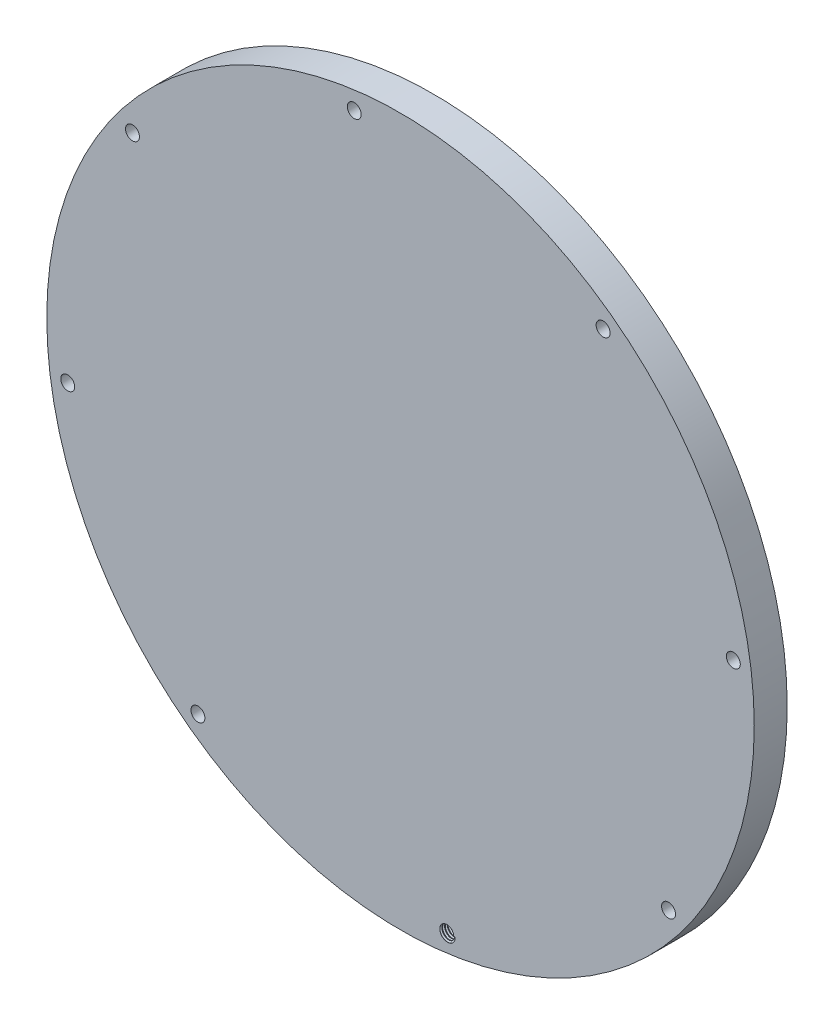
SolidWorks part; units mm, degrees
material "PVC rigide"
ref_plane "Plan de face" through (0, 0, 0) normal (0, 0, 1) x (1, 0, 0)
ref_plane "Plan de dessus" through (0, 0, 0) normal (0, 1, 0) x (1, 0, 0)
ref_plane "Plan de droite" through (0, 0, 0) normal (1, 0, 0) x (0, 0, -1)
sketch "Esquisse1" plane through (0, 0, 0) normal (0, 0, 1) x (1, 0, 0)
  circle A0 centre (0, 0) radius 139.5
  dimension "D1" = 279
extrude "Disque" add sketch "Esquisse1" along normal blind 13
sketch "Esquisse2" plane through (0, 0, 0) normal (0, 0, -1) x (-1, 0, 0)
  circle A0 centre (-79.8952, 105.7025) radius 2.75
  circle A1 centre (18.2485, 131.2373) radius 2.75
  circle A2 centre (105.7025, 79.8952) radius 2.75
  circle A3 centre (131.2373, -18.2485) radius 2.75
  circle A4 centre (79.8952, -105.7025) radius 2.75
  circle A5 centre (-18.2485, -131.2373) radius 2.75
  circle A6 centre (-105.7025, -79.8952) radius 2.75
  circle A7 centre (-131.2373, 18.2485) radius 2.75
  point P20 (0, 0)
  dimension "D1" = 5.5
  dimension "D2" = 132.5
  dimension "D4" = 0
  dimension "D3" = 8
extrude "Pas_De_Vis" cut sketch "Esquisse2" against normal blind 13
sketch "Esquisse4" plane through (0, 0, 0) normal (0, 0, -1) x (-1, 0, 0)
  circle A0 centre (0, 0) radius 120
  dimension "D1" = 240
extrude "Bain" cut sketch "Esquisse4" against normal blind 3
thread "Filetage1" pitch 1.0583 method cut profile "Profil de filetage1" start angle 0, offset 0, length 0, pitch 1.0583, diameter 5.5
ref_plane "Plan1" through (20.9985, -131.2373, 0) normal (0, -1, 0) x (1, 0, 0)
sketch "Profil de filetage1" plane through (20.9985, -131.2373, 0) normal (0, -1, 0) x (1, 0, 0)
  line L0 (0, 0) -> (0, 1.0583) construction
  line L1 (0, 0) -> (0.5728, 0.3307)
  line L2 (0.5728, 0.3307) -> (0.5728, 0.463)
  line L3 (0.5728, 0.463) -> (0, 0.7937)
  line L4 (0.5728, 0.3969) -> (0, 0.3969) construction
  line L11 (0, 0) -> (0, 0.7937)
  point P2 (0, 0)
  dimension "Pitch" = 1.0583
  dimension "Profile_Angle" = 60
  dimension "Profile_Land" = 0.1323
  dimension "Profile_Height" = 0.5728
sketch "Milieu" plane through (0, 0, 3) normal (0, 0, -1) x (-1, 0, 0)
  line L0 (0, -28.5) -> (0, 28.5) construction
  line L3 (28.5, -28.5) -> (28.5, 28.5)
  line L4 (-28.5, -28.5) -> (-28.5, 28.5)
  arc A0 (28.5, 28.5) -> (-28.5, 28.5) centre (0, 28.5) ccw
  arc A1 (28.5, -28.5) -> (-28.5, -28.5) centre (0, -28.5) cw
  point P7 (0, 0)
  point P8 (0, 28.5)
  dimension "D4" = 28.5
  dimension "D5" = 28.5
  dimension "D1" = 57
  dimension "D2" = 0
  dimension "D3" = 0
sketch "Est" plane through (0, 0, 3) normal (0, 0, -1) x (-1, 0, 0)
  line L0 (-53.5, -18.2035) -> (-53.5, 19.7965)
  line L1 (-91.4833, 19.0423) -> (-91.4833, -18.9577)
  line L2 (-72.4833, 19) -> (-72.4833, -19) construction
  line L3 (-28.5, -28.5) -> (-28.5, 28.5) construction
  arc A0 (-53.5, 19.7965) -> (-91.4833, 19.0423) centre (-72.4833, 19) ccw
  arc A1 (-91.4833, -18.9577) -> (-53.5, -18.2035) centre (-72.4833, -19) ccw
  point P6 (-72.4833, 0)
  point P9 (0, 0)
  point P13 (0, 0)
  dimension "D4" = 19
  dimension "D5" = 19
  dimension "D1" = 0
  dimension "D2" = 25
  dimension "D3" = 38
  dimension "D7" = 38
sketch "Ouest" plane through (0, 0, 3) normal (0, 0, -1) x (-1, 0, 0)
  line L0 (60, 14.25) -> (60, -14.25)
  line L1 (88.5, -14.25) -> (88.5, 14.25)
  line L2 (74.25, -14.25) -> (74.25, 14.25) construction
  arc A0 (60, -14.25) -> (88.5, -14.25) centre (74.25, -14.25) ccw
  arc A1 (88.5, 14.25) -> (60, 14.25) centre (74.25, 14.25) ccw
  point P6 (74.25, 0)
  dimension "D1" = 14.25
  dimension "D2" = 14.25
  dimension "D3" = 28.5
  dimension "D4" = 28.5
  dimension "D5" = 74.25
extrude "Milieu1" cut sketch "Milieu" against normal blind 3
extrude "Est1" cut sketch "Est" against normal blind 3
extrude "Ouest1" cut sketch "Ouest" against normal blind 3
sketch "Esquisse12" plane through (0, 0, 3) normal (0, 0, -1) x (-1, 0, 0)
  line L0 (-9.5, 85) -> (9.5, 85) construction
  line L1 (-9.5, 94.5) -> (9.5, 94.5)
  line L2 (-9.5, 75.5) -> (9.5, 75.5)
  arc A0 (-9.5, 94.5) -> (-9.5, 75.5) centre (-9.5, 85) ccw
  arc A1 (9.5, 75.5) -> (9.5, 94.5) centre (9.5, 85) ccw
  point P0 (0, 85)
  dimension "D2" = 19
  dimension "D1" = 9.5
  dimension "D3" = 9.5
  dimension "D4" = 0
  dimension "D5" = 85
extrude "Sud" cut sketch "Esquisse12" against normal blind 3
sketch "Esquisse14" plane through (0, 0, 3) normal (0, 0, -1) x (-1, 0, 0)
  line L0 (-7.125, -88.5) -> (7.125, -88.5) construction
  line L1 (-7.125, -81.375) -> (7.125, -81.375)
  line L2 (-7.125, -95.625) -> (7.125, -95.625)
  arc A0 (-7.125, -81.375) -> (-7.125, -95.625) centre (-7.125, -88.5) ccw
  arc A1 (7.125, -95.625) -> (7.125, -81.375) centre (7.125, -88.5) ccw
  point P0 (0, -88.5)
  dimension "D2" = 14.25
  dimension "D1" = 7.125
  dimension "D3" = 7.125
  dimension "D4" = 0
  dimension "D5" = 88.5
extrude "Nord" cut sketch "Esquisse14" against normal blind 3
